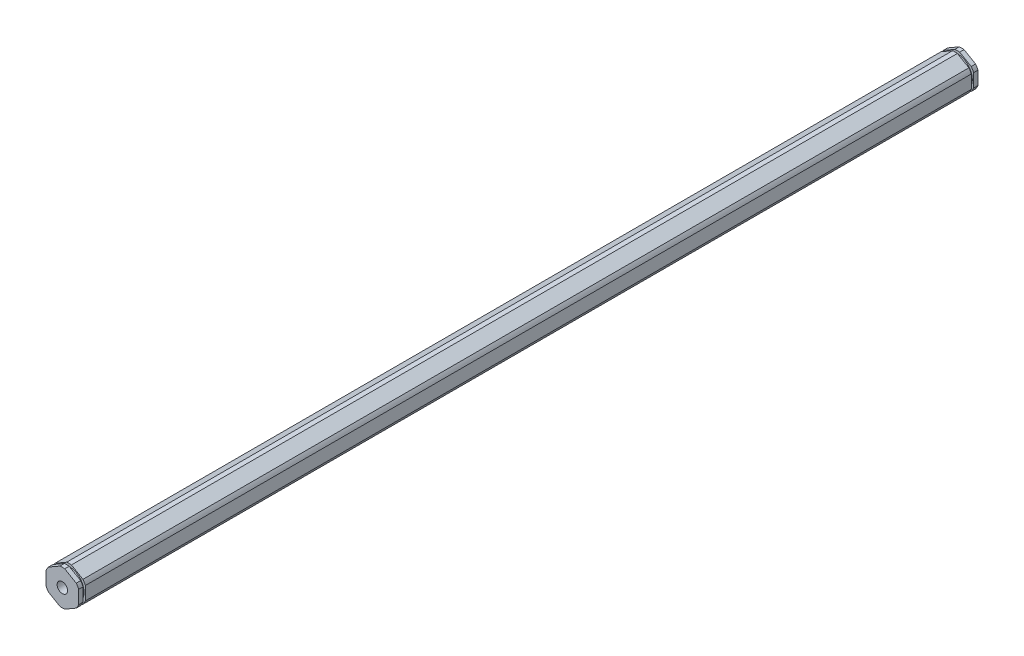
SolidWorks part; units mm, degrees
ref_plane "Front Plane" through (0, 0, 0) normal (0, 0, 1) x (1, 0, 0)
ref_plane "Top Plane" through (0, 0, 0) normal (0, 1, 0) x (1, 0, 0)
ref_plane "Right Plane" through (0, 0, 0) normal (1, 0, 0) x (0, 0, -1)
sketch "Sketch1" plane through (0, 0, 0) normal (0, 0, 1) x (1, 0, 0)
  line L1 (0, 7.3323) -> (-6.35, 3.6662)
  line L2 (-6.35, 3.6662) -> (-6.35, -3.6662)
  line L3 (-6.35, -3.6662) -> (0, -7.3323)
  line L4 (0, -7.3323) -> (6.35, -3.6662)
  line L5 (6.35, -3.6662) -> (6.35, 3.6662)
  line L6 (6.35, 3.6662) -> (0, 7.3323)
  circle A0 centre (0, 0) radius 6.35 construction
  circle A1 centre (0, 0) radius 6.858
  dimension "D1" = 12.7
  dimension "D2" = 13.716
extrude "Boss-Extrude1" add sketch "Sketch1" along normal mid plane 349.6945 contours L5 A1 L6 L1 L2 L3 L4 region at (0, 0, 0)
hole_wizard "#10-32 Tapped Hole1" positions "3DSketch1" profile "Sketch2" tap size "#10-32" standard "ANSI Inch"
sketch3d "3DSketch1"
  line L0 (0, 0, 174.8473) -> (0, 0, -174.8473) construction
  line L1 (0, 0, 174.8473) -> (0, 0, -174.8473) construction
  point P0 (0, 0, 174.8473)
  point P4 (0, 0, -174.8473)
sketch "Sketch2" plane through (0, 0, 174.8473) normal (1, 0, 0) x (0, -1, 0)
  line L0 (0, 0) -> (0, 17.5608)
  line L1 (0, 17.5608) -> (2.0193, 16.3474)
  line L2 (2.0193, 16.3474) -> (2.0193, 0)
  line L5 (2.0193, 0) -> (0, 0)
  line L10 (0, 17.5608) -> (-2.0193, 16.3474) construction
  line L11 (0, -6.35) -> (0, 107.95) construction
  dimension "Tap Drill Dia." = 4.0386
  dimension "Tap Drill Depth" = 16.3474
  dimension "Drill Angle" = 118
cosmetic thread "Hole Thread1" parameters "D1"=13.97, "D2"=4.826
cosmetic thread "Hole Thread2" parameters "D1"=13.97, "D2"=4.826
sketch "Sketch3" plane through (0, 0, 0) normal (1, 0, 0) x (0, 0, -1)
  line L0 (-175.1574, 0) -> (-171.1173, 0) construction
  line L1 (174.8472, 6.858) -> (-174.8473, 6.858) construction
  line L2 (-173.1328, 6.858) -> (-172.2438, 6.858)
  line L3 (-173.1328, 6.858) -> (-173.1328, 5.8547)
  line L4 (-173.1328, 5.8547) -> (-172.2438, 5.8547)
  line L5 (-172.2438, 6.858) -> (-172.2438, 5.8547)
  dimension "D1" = 0.889
  dimension "D2" = 5.8547
  dimension "D3" = 1.7145
revolve "Cut-Revolve1" cut sketch "Sketch3" angle 360 about L0
mirror "Mirror1" about plane through (0, 0, 0) normal (0, 0, 1) of "Cut-Revolve1"
